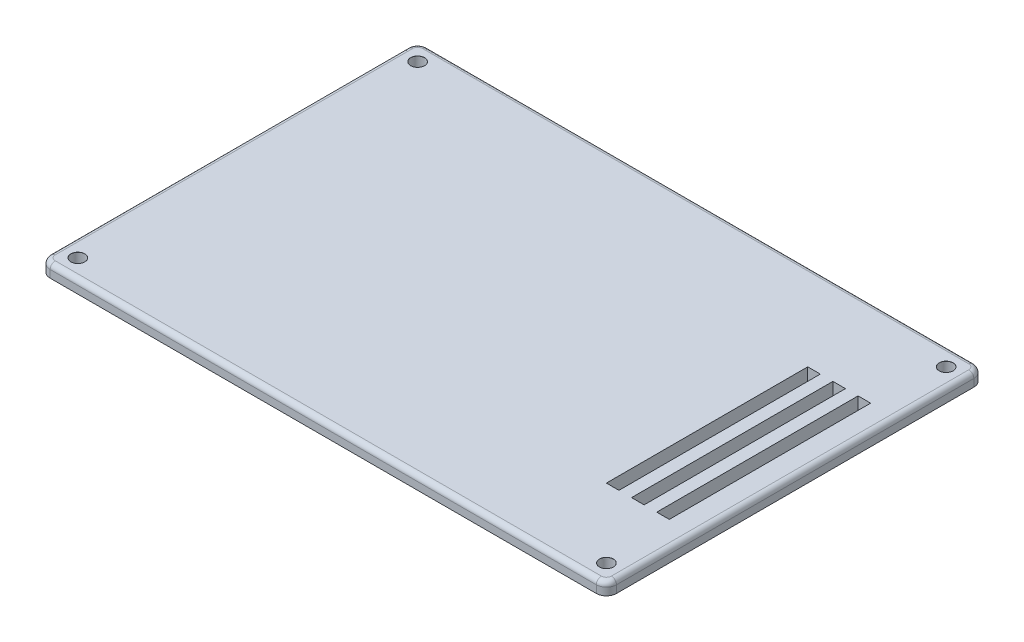
SolidWorks part; units mm, degrees
ref_plane "Front Plane" through (0, 0, 0) normal (0, 0, 1) x (1, 0, 0)
ref_plane "Top Plane" through (0, 0, 0) normal (0, 1, 0) x (1, 0, 0)
ref_plane "Right Plane" through (0, 0, 0) normal (1, 0, 0) x (0, 0, -1)
sketch "Sketch1" plane through (0, 0, 0) normal (0, 1, 0) x (1, 0, 0)
  line L1 (-112.5, 75) -> (112.5, 75)
  line L2 (-112.5, 75) -> (-112.5, -75)
  line L3 (-112.5, -75) -> (112.5, -75)
  line L4 (112.5, 75) -> (112.5, -75)
  line L5 (-112.5, 75) -> (112.5, -75) construction
  line L6 (-112.5, -75) -> (112.5, 75) construction
  line L7 (97.5, 40) -> (102.5, 40)
  line L8 (97.5, 40) -> (97.5, -40)
  line L9 (97.5, -40) -> (102.5, -40)
  line L10 (102.5, 40) -> (102.5, -40)
  line L11 (87.5, 40) -> (92.5, 40)
  line L12 (87.5, 40) -> (87.5, -40)
  line L13 (87.5, -40) -> (92.5, -40)
  line L14 (92.5, 40) -> (92.5, -40)
  line L15 (77.5, 40) -> (82.5, 40)
  line L16 (77.5, 40) -> (77.5, -40)
  line L17 (77.5, -40) -> (82.5, -40)
  line L18 (82.5, 40) -> (82.5, -40)
  point P0 (0, 0)
  point P20 (102.5, 0)
  point P21 (112.5, 0)
  dimension "D1" = 150
  dimension "D2" = 225
  dimension "D3" = 80
  dimension "D4" = 5
  dimension "D5" = 5
  dimension "D6" = 5
  dimension "D7" = 10
extrude "Boss-Extrude1" add sketch "Sketch1" along normal blind 5
hole_wizard "M5 Clearance Hole1" positions "Sketch2" profile "Sketch3" hole size "M5" standard "ANSI Metric" end condition through all
sketch "Sketch2" plane through (0, 5, 0) normal (0, 1, 0) x (1, 0, 0)
  line L1 (-105, 67.5) -> (105, 67.5) construction
  line L2 (105, 67.5) -> (105, -67.5) construction
  line L3 (105, -67.5) -> (-105, -67.5) construction
  line L4 (-105, -67.5) -> (-105, 67.5) construction
  line L6 (-112.5, 75) -> (-112.5, -75) construction
  line L7 (112.5, -75) -> (112.5, 75) construction
  line L8 (112.5, 75) -> (-112.5, 75) construction
  line L9 (-112.5, -75) -> (112.5, -75) construction
  point P0 (-105, 67.5)
  point P2 (105, 67.5)
  point P4 (-105, -67.5)
  point P6 (105, -67.5)
  dimension "D1" = 7.5
  dimension "D2" = 7.5
  dimension "D3" = 7.5
  dimension "D4" = 7.5
sketch "Sketch3" plane through (-105, 5, -67.5) normal (1, 0, 0) x (0, 0, 1)
  line L0 (0, 0) -> (0, 5)
  line L1 (0, 5) -> (2.75, 5)
  line L2 (2.75, 5) -> (2.75, 0.025)
  line L3 (2.75, 0.025) -> (2.775, 0)
  line L5 (2.775, 0) -> (0, 0)
  line L6 (-2.75, 0.025) -> (-2.775, 0) construction
  line L11 (0, -6.35) -> (0, 107.95) construction
  dimension "Thru Hole Dia." = 5.5
  dimension "Thru Hole Depth" = 5
  dimension "Near C'Sink Dia." = 5.55
  dimension "Near C'Sink Angle" = 90
fillet "Fillet1" radius 2 4 edges at (112.5, 5, 0) (0, 5, -75) (-112.5, 5, 0) (0, 5, 75)
fillet "Fillet2" radius 4 8 edges at (-111.9142, 4.4142, 74.4142) (-111.9142, 4.4142, -74.4142) (111.9142, 4.4142, -74.4142) (111.9142, 4.4142, 74.4142) (112.5, 1.5, 75) (112.5, 1.5, -75) (-112.5, 1.5, -75) (-112.5, 1.5, 75)
